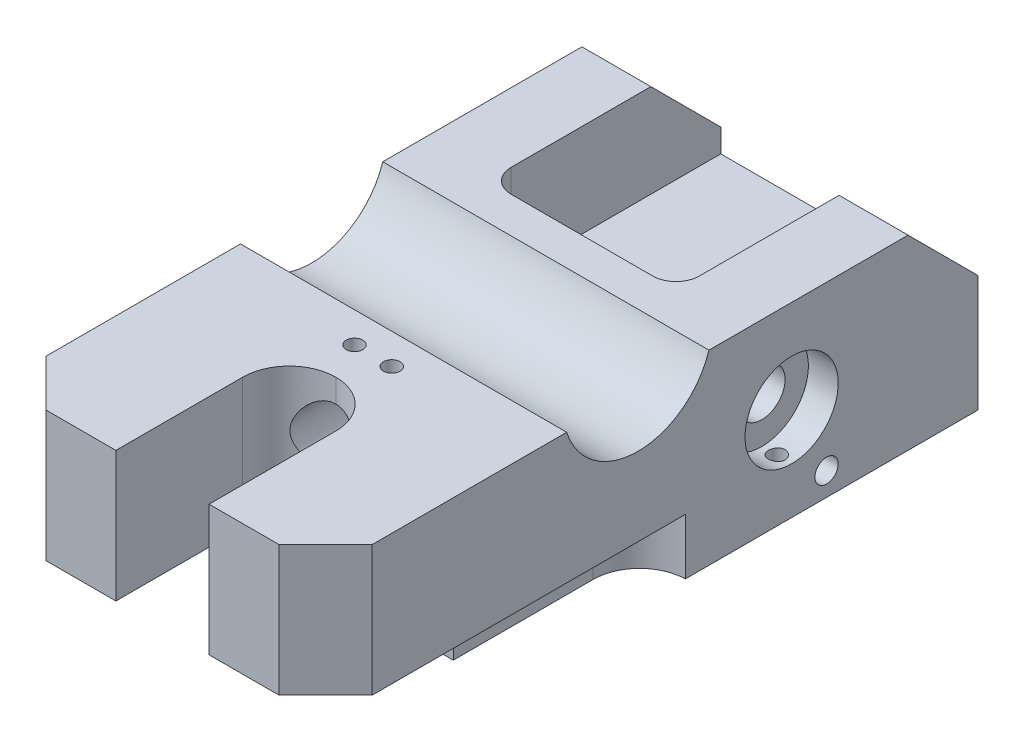
SolidWorks part; units mm, degrees
material "2024 Alloy"
ref_plane "Front Plane" through (0, 0, 0) normal (0, 0, 1) x (1, 0, 0)
ref_plane "Top Plane" through (0, 0, 0) normal (0, 1, 0) x (1, 0, 0)
ref_plane "Right Plane" through (0, 0, 0) normal (1, 0, 0) x (0, 0, -1)
sketch "Sketch1" plane through (0, 0, 0) normal (0, 1, 0) x (1, 0, 0)
  line L1 (-22.225, -44.45) -> (22.225, -44.45)
  line L2 (-22.225, -44.45) -> (-22.225, 44.45)
  line L3 (-22.225, 44.45) -> (22.225, 44.45)
  line L4 (22.225, -44.45) -> (22.225, 44.45)
  line L5 (-22.225, -44.45) -> (22.225, 44.45) construction
  line L6 (-22.225, 44.45) -> (22.225, -44.45) construction
  point P0 (0, 0)
  dimension "D1" = 44.45
  dimension "D2" = 88.9
extrude "Base" add sketch "Sketch1" along normal blind 12.7 and the other way blind 12.7
sketch "Sketch2" plane through (0, 0, -44.45) normal (0, 0, -1) x (-1, 0, 0)
  line L1 (-22.225, -12.7) -> (22.225, -12.7) construction
  circle A0 centre (0, -12.7) radius 4.7625
  dimension "D1" = 9.525
extrude "ShaftGuide" cut sketch "Sketch2" against normal blind 25.4
ref_plane "Plane1" through (0, -12.7, 0) normal (0, -1, 0) x (-1, 0, 0)
sketch "Sketch3" plane through (0, -12.7, 0) normal (0, -1, 0) x (-1, 0, 0)
  line L0 (10.922, -20.828) -> (16.002, -20.828)
  line L1 (22.225, -44.45) -> (-22.225, -44.45) construction
  line L2 (-22.225, -44.45) -> (-22.225, 44.45) construction
  line L3 (0, 0) -> (0, 102.0916) construction
  line L4 (-10.922, -20.828) -> (-16.002, -20.828)
  line L5 (-10.922, -20.828) -> (-10.922, 10.922)
  line L6 (-22.225, -44.45) -> (22.225, -44.45)
  line L7 (-10.922, 10.922) -> (10.922, 10.922)
  line L8 (10.922, -20.828) -> (10.922, 10.922)
  line L9 (-16.002, -20.828) -> (-16.002, 4.572)
  line L10 (-16.002, 4.572) -> (-22.225, 4.572)
  line L11 (-22.225, -44.45) -> (-22.225, -3.175)
  line L12 (-22.225, 4.572) -> (-22.225, -3.175)
  line L13 (22.225, -44.45) -> (22.225, -3.175)
  line L14 (4.7625, 44.45) -> (4.7625, 19.05)
  line L15 (4.7625, 19.05) -> (-4.7625, 19.05)
  line L16 (-4.7625, 19.05) -> (-4.7625, 44.45)
  line L17 (-4.7625, 44.45) -> (-22.225, 44.45)
  line L18 (-22.225, 44.45) -> (-22.225, -44.45)
  line L19 (-22.225, -44.45) -> (22.225, -44.45)
  line L20 (22.225, -44.45) -> (22.225, 44.45)
  line L21 (22.225, 44.45) -> (4.7625, 44.45)
  line L22 (16.002, -20.828) -> (16.002, 4.572)
  line L23 (22.225, 44.45) -> (22.225, -44.45) construction
  line L24 (22.225, 4.572) -> (22.225, -3.175)
  line L25 (-4.7625, 44.45) -> (-22.225, 44.45) construction
  line L26 (22.225, 4.572) -> (16.002, 4.572)
  line L28 (22.225, -44.45) -> (22.225, 44.45) construction
  line L29 (22.225, 44.45) -> (4.7625, 44.45) construction
  dimension "D6" = 21.844
  dimension "D9" = 31.75
  dimension "D2" = 5.08
  dimension "D3" = 33.528
  dimension "D4" = 6.35
  dimension "D1" = 0
extrude "ActuatorPlaneCut" cut sketch "Sketch3" against normal blind 7.62
sketch "Sketch5" plane through (0, 0, 0) normal (0, 1, 0) x (1, 0, 0)
  line L0 (-4.7625, 44.45) -> (-22.225, 44.45) construction
  line L1 (12.827, 25.4) -> (-12.827, 25.4)
  line L2 (12.827, 12.7) -> (12.827, 25.4)
  line L3 (12.827, 12.7) -> (-12.827, 12.7)
  line L4 (0, 0) -> (0, 121.8983) construction
  line L6 (-12.827, 12.7) -> (-12.827, 25.4)
  point P17 (12.827, 12.7)
  point P20 (12.827, 25.4)
  dimension "D1" = 12.7
  dimension "D2" = 25.654
  dimension "D4" = 19.05
extrude "WireChannel" cut sketch "Sketch5" along normal through all and the other way through all
fillet "Fillet1" radius 3.175 4 edges at (-12.827, 0, -25.4) (-12.827, 0, -12.7) (12.827, 0, -12.7) (12.827, 0, -25.4)
sketch "Sketch40" plane through (0, -12.7, 0) normal (0, -1, 0) x (1, 0, 0)
  line L1 (10.922, -15.24) -> (-10.922, -15.24)
  line L2 (10.922, -15.24) -> (10.922, 17.653)
  line L3 (7.747, 20.828) -> (-7.747, 20.828)
  line L4 (-10.922, -15.24) -> (-10.922, 17.653)
  line L6 (10.922, -10.922) -> (10.922, 20.828) construction
  line L7 (-9.652, -12.7) -> (9.652, -12.7) construction
  arc A0 (-7.747, 20.828) -> (-10.922, 17.653) centre (-7.747, 17.653) ccw
  arc A1 (7.747, 20.828) -> (10.922, 17.653) centre (7.747, 17.653) cw
  point P8 (-10.922, 20.828)
  dimension "D1" = 3.175
  dimension "D2" = 2.54
extrude "GearBoxPit" cut sketch "Sketch40" against normal blind 11.176
sketch "Sketch60" plane through (0, 12.7, 0) normal (0, 1, 0) x (1, 0, 0)
  line L0 (22.225, 44.45) -> (-22.225, 44.45) construction
  line L1 (-12.827, 22.225) -> (12.827, 22.225)
  line L2 (-12.827, 22.225) -> (-12.827, 44.45)
  line L3 (-12.827, 44.45) -> (12.827, 44.45)
  line L4 (12.827, 22.225) -> (12.827, 44.45)
  line L5 (12.827, 15.875) -> (12.827, 22.225) construction
extrude "FrontCutaway" cut sketch "Sketch60" against normal blind 12.7
chamfer "ChamferFront" distance 9.525 angle 45 2 edges at (-17.526, 12.7, -44.45) (17.526, 12.7, -44.45)
sketch "Sketch22" plane through (0, -12.7, 0) normal (0, -1, 0) x (1, 0, 0)
  line L0 (2.413, 17.4149) -> (-2.413, 17.4149) construction
  line L1 (2.413, 6.7469) -> (-2.413, 6.7469) construction
  line L2 (2.413, 17.8118) -> (-2.413, 17.8118)
  line L3 (2.413, 17.018) -> (-2.413, 17.018)
  line L4 (2.413, 6.35) -> (-2.413, 6.35)
  line L5 (2.413, 7.1438) -> (-2.413, 7.1438)
  line L6 (0, -39.4682) -> (0, -19.7785) construction
  line L7 (10.922, 12.0809) -> (-10.922, 12.0809) construction
  line L8 (10.922, -12.9651) -> (10.922, 20.828) construction
  line L9 (-10.922, 20.828) -> (-10.922, -12.9651) construction
  line L11 (-9.652, -12.7) -> (9.652, -12.7) construction
  arc A0 (2.413, 6.35) -> (2.413, 7.1438) centre (2.413, 6.7469) ccw
  arc A1 (-2.413, 7.1438) -> (-2.413, 6.35) centre (-2.413, 6.7469) ccw
  arc A2 (2.413, 17.8118) -> (2.413, 17.018) centre (2.413, 17.4149) cw
  arc A3 (-2.413, 17.018) -> (-2.413, 17.8118) centre (-2.413, 17.4149) cw
  point P6 (0, 6.7469)
  point P17 (0, 17.4149)
  dimension "D1" = 0.7937
  dimension "D2" = 4.826
  dimension "D3" = 10.668
  dimension "D4" = 19.05
extrude "GearBoxSlots" cut sketch "Sketch22" against normal blind 13.716
sketch "Sketch55" plane through (-22.225, 0, 0) normal (-1, 0, 0) x (0, 0, 1)
  line L0 (-44.45, -12.7) -> (-4.572, -12.7) construction
  line L1 (-25.4, -12.7) -> (-25.4, -7.9375) construction
  circle A0 centre (-23.8125, -9.525) radius 1.5875
  dimension "D1" = 3.175
  dimension "D2" = 3.175
extrude "GuideBarHole" cut sketch "Sketch55" against normal through all
sketch "Sketch56" plane through (0, 0, 0) normal (1, 0, 0) x (0, 0, -1)
  line L0 (22.225, -12.7) -> (15.875, -12.7) construction
  line L1 (22.225, -12.7) -> (15.875, -12.7) construction
  line L2 (19.05, -12.7) -> (19.05, 12.7) construction
  line L3 (34.925, 12.7) -> (-44.45, 12.7) construction
  circle A0 centre (19.05, 0) radius 3.175
  dimension "D1" = 6.35
extrude "PitchShaftHole" cut sketch "Sketch56" against normal through all and the other way through all
sketch "Sketch57" plane through (-22.225, 0, 0) normal (-1, 0, 0) x (0, 0, 1)
  circle A0 centre (-19.05, 0) radius 6.35
  circle A1 centre (-19.05, 0) radius 3.175 construction
  dimension "D1" = 12.7
extrude "BearingBoreR" cut sketch "Sketch57" against normal blind 4.064
mirror "BearingBoreL" about plane through (0, 0, 0) normal (1, 0, 0) of "BearingBoreR"
hole_wizard "BearingBoreSetScrews" positions "Sketch59" profile "Sketch58" tap size "#4-40" standard "ANSI Inch" end condition up to next
sketch "Sketch59" plane through (-13.4063, -12.7, -12.9307) normal (0, 1, 0) x (1, 0, 0)
  line L5 (-8.8187, 12.4693) -> (-8.8187, -0.2307) construction
  line L6 (-8.8187, 12.4693) -> (-8.8187, -0.2307) construction
  line L7 (-8.8187, 6.1193) -> (35.6313, 6.1193) construction
  line L8 (35.6313, -57.3807) -> (35.6313, 21.9943) construction
  line L10 (-8.8187, 21.9943) -> (-8.8187, -57.3807) construction
  point P0 (-6.7867, 6.1193)
  point P2 (33.5993, 6.1193)
  dimension "D1" = 2.032
  dimension "D2" = 2.032
sketch "Sketch58" plane through (-20.193, -12.7, -19.05) normal (1, 0, 0) x (0, 0, -1)
  line L0 (0, 0) -> (0, 6.35)
  line L1 (0, 6.35) -> (1.1303, 6.35)
  line L2 (1.1303, 6.35) -> (1.1303, 0)
  line L5 (1.1303, 0) -> (0, 0)
  line L11 (0, -6.35) -> (0, 107.95) construction
  dimension "Thru Tap Drill Dia." = 2.2606
  dimension "Thru Tap Drill Depth" = 6.35
cosmetic thread "Hole Thread18" parameters "D2"=2.8448
cosmetic thread "Hole Thread19" parameters "D2"=2.8448
hole_wizard "ToggleAssemHoles" positions "Sketch50" profile "Sketch49" tap size "#6-32" standard "ANSI Inch"
sketch "Sketch50" plane through (0, -12.7, 0) normal (0, -1, 0) x (-1, 0, 0)
  line L0 (-22.225, 44.45) -> (-4.7625, 44.45) construction
  line L1 (4.7625, 44.45) -> (-4.7625, 44.45) construction
  line L2 (0, 0) -> (0, 49.3678) construction
  point P0 (12.7, 38.1)
  point P2 (-12.7, 38.1)
  point P8 (0, 44.45)
  dimension "D1" = 6.35
  dimension "D2" = 12.7
sketch "Sketch49" plane through (-12.7, -12.7, -38.1) normal (1, 0, 0) x (0, 0, -1)
  line L0 (0, 0) -> (0, 10.2107)
  line L1 (0, 10.2107) -> (1.3525, 9.398)
  line L2 (1.3525, 9.398) -> (1.3525, 0)
  line L5 (1.3525, 0) -> (0, 0)
  line L10 (0, 10.2107) -> (-1.3526, 9.398) construction
  line L11 (0, -6.35) -> (0, 107.95) construction
  dimension "Tap Drill Dia." = 2.7051
  dimension "Tap Drill Depth" = 9.398
  dimension "Drill Angle" = 118
cosmetic thread "Hole Thread12" parameters "D1"=9.398, "D2"=3.5052
cosmetic thread "Hole Thread13" parameters "D1"=9.398, "D2"=3.5052
sketch "Sketch39" plane through (0, 12.7, 0) normal (0, 1, 0) x (1, 0, 0)
  line L0 (7.747, -20.828) -> (-7.747, -20.828) construction
  line L1 (-6.35, -97.028) -> (6.35, -97.028)
  line L2 (-6.35, -97.028) -> (-6.35, -27.1755)
  line L3 (-0.0025, -20.828) -> (0.0025, -20.828)
  line L4 (6.35, -97.028) -> (6.35, -27.1755)
  line L5 (-6.35, -97.028) -> (6.35, -20.828) construction
  line L6 (-6.35, -20.828) -> (6.35, -97.028) construction
  arc A0 (0.0025, -20.828) -> (6.35, -27.1755) centre (0.0025, -27.1755) cw
  arc A1 (-6.35, -27.1755) -> (-0.0025, -20.828) centre (-0.0025, -27.1755) cw
  point P0 (0, -58.928)
  point P7 (0, 0)
  dimension "D3" = 6.3475
  dimension "D1" = 12.7
  dimension "D2" = 76.2
extrude "GripSlot" cut sketch "Sketch39" against normal blind 18.288
sketch "Sketch51" plane through (0, 0, 44.45) normal (0, 0, -1) x (-1, 0, 0)
  line L0 (9.652, 12.7) -> (-9.652, 12.7) construction
  circle A0 centre (0, 5.08) radius 4.445
  dimension "D2" = 8.89
  dimension "D1" = 7.62
extrude "LinActHole" cut sketch "Sketch51" along normal up to surface (38.1 mm away) up to face at (0, -0.254, 6.35)
hole_wizard "LinActSetHoles" positions "Sketch54" profile "Sketch53" tap size "#4-40" standard "ANSI Inch" end condition up to next
sketch "Sketch54" plane through (0, 12.7, 0) normal (0, 1, 0) x (1, 0, 0)
  line L0 (0, 0) -> (0, -17.2208) construction
  point P0 (2.54, -15.748)
  point P2 (-2.54, -15.748)
  dimension "D1" = 5.08
  dimension "D4" = 5.08
sketch "Sketch53" plane through (2.54, 12.7, 15.748) normal (1, 0, 0) x (0, 0, 1)
  line L0 (0, 0) -> (0, 3.9722)
  line L1 (0, 3.9722) -> (1.1303, 3.9722)
  line L2 (1.1303, 3.9722) -> (1.1303, 0)
  line L5 (1.1303, 0) -> (0, 0)
  line L11 (0, -6.35) -> (0, 107.95) construction
  dimension "Thru Tap Drill Dia." = 2.2606
  dimension "Thru Tap Drill Depth" = 3.9722
cosmetic thread "Hole Thread16" parameters "D2"=2.8448
cosmetic thread "Hole Thread17" parameters "D2"=2.8448
sketch "Sketch44" plane through (0, 12.7, 0) normal (0, 1, 0) x (1, 0, 0)
  line L0 (22.225, -6.35) -> (22.225, -44.45)
  line L1 (12.7, -44.45) -> (12.7, -15.875)
  line L2 (6.35, -44.45) -> (22.225, -44.45) construction
  line L3 (22.225, -44.45) -> (22.225, 34.925) construction
  line L4 (22.225, -44.45) -> (12.7, -44.45)
  line L5 (0, 0) -> (0, -86.719) construction
  line L6 (-22.225, -44.45) -> (-12.7, -44.45)
  line L7 (-12.7, -44.45) -> (-12.7, -15.875)
  line L8 (-22.225, -6.35) -> (-22.225, -44.45)
  line L9 (-22.225, 34.925) -> (-22.225, -44.45) construction
  line L10 (22.225, 4.572) -> (22.225, -44.45) construction
  arc A0 (22.225, -6.35) -> (12.7, -15.875) centre (22.225, -15.875) ccw
  arc A1 (-22.225, -6.35) -> (-12.7, -15.875) centre (-22.225, -15.875) cw
  dimension "D2" = 38.1
  dimension "D3" = 9.525
extrude "RoundCutAways" [suppressed] cut sketch "Sketch44" against normal through all
chamfer "Chamfer1" [suppressed] distance 6.35 angle 45
chamfer "Chamfer2" distance 6.35 angle 45 2 edges at (22.225, 3.81, 44.45) (-22.225, 3.81, 44.45)
fillet "Fillet2" radius 6.35 2 edges at (-16.002, -8.89, -4.572) (16.002, -8.89, -4.572)
sketch "Sketch62" plane through (-22.225, 0, 0) normal (-1, 0, 0) x (0, 0, 1)
  line L0 (-44.45, -12.7) -> (-44.45, 3.175) construction
  line L1 (-34.925, 12.7) -> (38.1, 12.7) construction
  circle A0 centre (1.905, 15.748) radius 10.16
  dimension "D1" = 20.32
  dimension "D2" = 46.355
  dimension "D3" = 3.048
extrude "Cut-Extrude2" cut sketch "Sketch62" against normal through all
